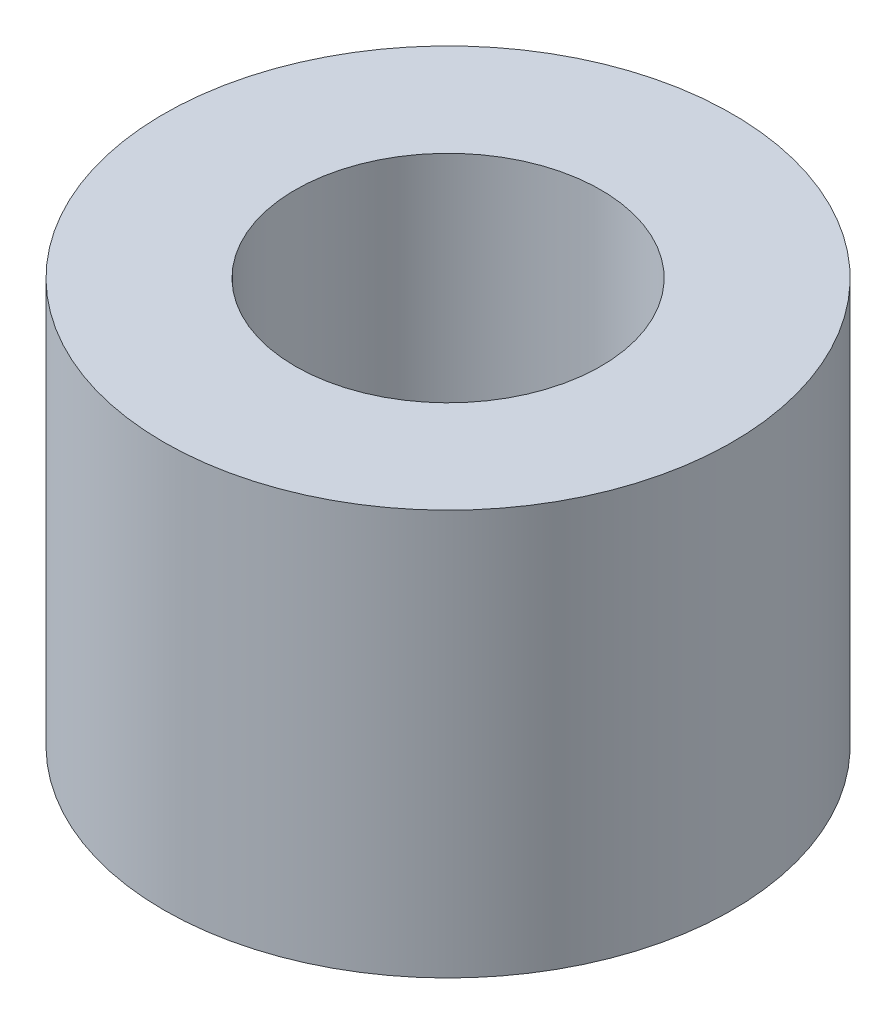
SolidWorks part; units mm, degrees
ref_plane "Front Plane" through (0, 0, 0) normal (0, 0, 1) x (1, 0, 0)
ref_plane "Top Plane" through (0, 0, 0) normal (0, 1, 0) x (1, 0, 0)
ref_plane "Right Plane" through (0, 0, 0) normal (1, 0, 0) x (0, 0, -1)
ref_plane "Mid Plane" through (0, 9.225, 0) normal (0, 1, 0) x (1, 0, 0)
sketch "Spacer Sketch" plane through (0, 9.225, 0) normal (0, 1, 0) x (1, 0, 0)
  circle A0 centre (0, -13.44) radius 4
  circle A1 centre (0, -13.44) radius 2.15
extrude "Spacer" add sketch "Spacer Sketch" along normal mid plane 5.7
ref_axis "Engine Axis" through (4.4, 0, 0) along (-1, 0, 0)
